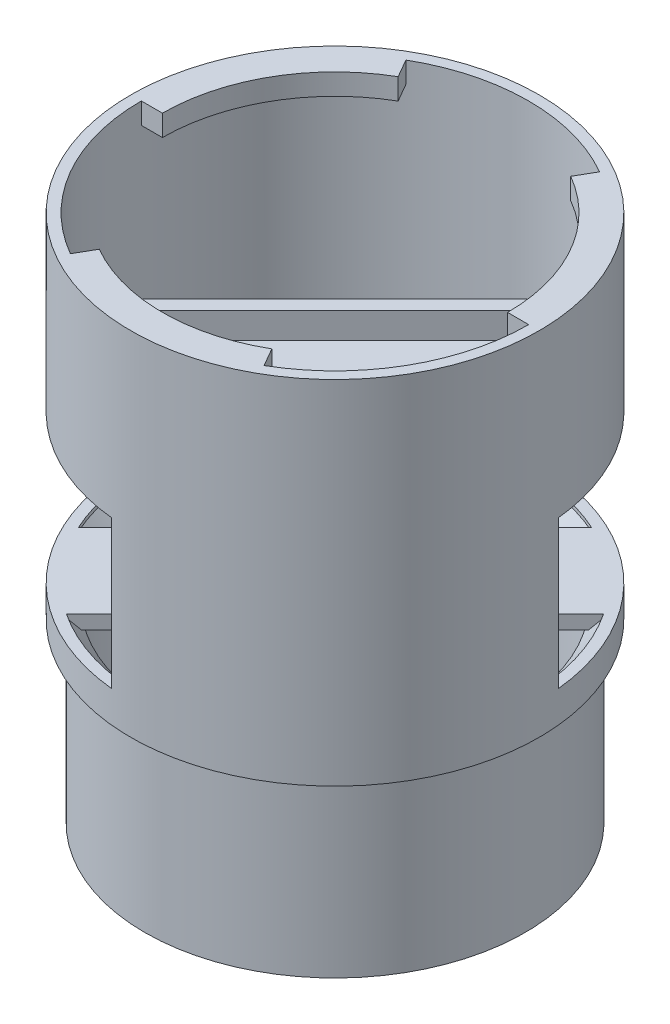
SolidWorks part; units mm, degrees
ref_plane "Front Plane" through (0, 0, 0) normal (0, 0, 1) x (1, 0, 0)
ref_plane "Top Plane" through (0, 0, 0) normal (0, 1, 0) x (1, 0, 0)
ref_plane "Right Plane" through (0, 0, 0) normal (1, 0, 0) x (0, 0, -1)
sketch "Sketch1" plane through (0, 0, 0) normal (0, 1, 0) x (1, 0, 0)
  circle A0 centre (0, 0) radius 25.5
  circle A1 centre (0, 0) radius 27
  dimension "D1" = 54
  dimension "D2" = 1.5
extrude "Boss-Extrude3" add sketch "Sketch1" along normal blind 25
sketch "Sketch3" plane through (0, 0, 0) normal (0, -1, 0) x (1, 0, 0)
  line L0 (-25.5, 0) -> (25.5, 0) construction
  line L1 (0, 25.5) -> (0, -25.5) construction
  line L2 (-25.1843, 4) -> (-14.4568, 4)
  line L3 (-4, 14.4568) -> (-4, 25.1843)
  line L4 (14.4568, 4) -> (25.1843, 4)
  line L5 (4, 25.1843) -> (4, 14.4568)
  line L6 (4, -14.4568) -> (4, -25.1843)
  line L7 (25.1843, -4) -> (14.4568, -4)
  line L8 (-14.4568, -4) -> (-25.1843, -4)
  line L9 (-4, -25.1843) -> (-4, -14.4568)
  circle A0 centre (0, 0) radius 25.5 construction
  arc A1 (-25.1843, 4) -> (-25.1843, -4) centre (0, 0) ccw
  arc A2 (4, 25.1843) -> (-4, 25.1843) centre (0, 0) ccw
  arc A3 (25.1843, -4) -> (25.1843, 4) centre (0, 0) ccw
  arc A4 (-4, -25.1843) -> (4, -25.1843) centre (0, 0) ccw
  circle A5 centre (-10, 0) radius 1.75
  circle A6 centre (0, 10) radius 1.75
  circle A7 centre (10, 0) radius 1.75
  circle A8 centre (0, -10) radius 1.75
  circle A9 centre (0, 0) radius 5
  arc A10 (-14.4568, -4) -> (-4, -14.4568) centre (0, 0) ccw
  arc A11 (-4, 14.4568) -> (-14.4568, 4) centre (0, 0) ccw
  arc A12 (14.4568, 4) -> (4, 14.4568) centre (0, 0) ccw
  arc A13 (4, -14.4568) -> (14.4568, -4) centre (0, 0) ccw
  point P22 (0, 0)
  point P32 (0, 0)
  dimension "D4" = 3.5
  dimension "D7" = 10
  dimension "D8" = 30
  dimension "D1" = 4
  dimension "D2" = 4
  dimension "D5" = 10
  dimension "D3" = 4
  dimension "D6" = 4
extrude "Boss-Extrude4" add sketch "Sketch3" against normal blind 6
ref_plane "Plane1" through (0, 0, 0) normal (-0.7071, 0, 0.7071) x (0.7071, 0, 0.7071)
sketch "Sketch4" plane through (0, 0, 0) normal (-0.7071, 0, 0.7071) x (0.7071, 0, 0.7071)
  line L0 (0, 0) -> (0, 105.4419) construction
  line L1 (-27, 25) -> (-29, 25)
  line L2 (27, 25) -> (-27, 25) construction
  line L3 (-20.2823, 75) -> (15.9379, 75) construction
  line L4 (25.5, 25) -> (-25.5, 25) construction
  line L5 (-29, 25) -> (-29, 75)
  line L6 (-29, 75) -> (-27.5, 75)
  line L7 (-27.5, 75) -> (-27.5, 29)
  line L8 (-27.5, 29) -> (-25.5, 27)
  line L9 (-29, 41.2871) -> (-29, 82.0597) construction
  line L10 (-25.5, 27) -> (-25.5, 25)
  line L11 (-25.5, 25) -> (-27, 25)
  line L15 (0, 75) -> (0, 73.5)
  line L16 (0, 75) -> (0, 73.5)
  dimension "D1" = 50
  dimension "D2" = 29
  dimension "D3" = 1.5
  dimension "D4" = 50
  dimension "D5" = 2
  dimension "D6" = 135
revolve "Revolve1" add sketch "Sketch4" angle 360 about L0 region at (-19.8899, 48.2634, -19.8899)
sketch "Sketch5" plane through (0, 0, 0) normal (-0.7071, 0, 0.7071) x (0.7071, 0, 0.7071)
  line L0 (0, 82.5379) -> (0.5211, 25.5117) construction
  line L2 (-17.6113, 29.5) -> (18.3887, 29.5)
  line L3 (-17.6113, 29.5) -> (-17.6113, 50.5)
  line L4 (-17.6113, 50.5) -> (18.3887, 50.5)
  line L5 (18.3887, 29.5) -> (18.3887, 50.5)
  line L6 (-17.6113, 29.5) -> (18.3887, 50.5) construction
  line L7 (-17.6113, 50.5) -> (18.3887, 29.5) construction
  line L8 (27.5, 29) -> (-27.5, 29) construction
  point P2 (0.3887, 40)
  dimension "D1" = 11
  dimension "D2" = 21
  dimension "D3" = 36
extrude "Cut-Extrude1" cut sketch "Sketch5" against normal through all both and the other way through all
sketch "Sketch6" plane through (0, 0, 0) normal (-0.7071, 0, 0.7071) x (0.7071, 0, 0.7071)
  line L2 (-17.6113, 50.5) -> (18.3887, 50.5) construction
  line L6 (-19.6113, 29.5) -> (-17.6113, 29.5)
  line L8 (-9.6113, 29.5) -> (5.3887, 29.5)
  line L9 (5.3887, 29.5) -> (5.3887, 27.5)
  line L10 (5.3887, 27.5) -> (-9.6113, 27.5)
  line L11 (-9.6113, 27.5) -> (-9.6113, 29.5)
  line L14 (-17.6113, 29.5) -> (-17.6113, 50.5)
  line L15 (-17.6113, 50.5) -> (-19.6113, 50.5)
  line L16 (-19.6113, 50.5) -> (-19.6113, 29.5)
  line L17 (-9.6113, 50.5) -> (-9.6113, 52.5)
  line L19 (-9.6113, 52.5) -> (5.83, 52.5)
  line L20 (5.83, 52.5) -> (5.83, 50.5)
  line L21 (5.83, 50.5) -> (-9.6113, 50.5)
  dimension "D1" = 2
  dimension "D2" = 2
  dimension "D3" = 21
  dimension "D4" = 2
  dimension "D5" = 15
  dimension "D6" = 8
extrude "Boss-Extrude6" add sketch "Sketch6" against normal up to next and the other way up to next
sketch "Sketch7" plane through (0, 75, 0) normal (0, 1, 0) x (1, 0, 0)
  line L0 (-29, 0) -> (29, 0) construction
  line L1 (-27.5, 0) -> (-24.5, 0)
  line L2 (-12.25, 21.2176) -> (-13.75, 23.8157)
  circle A0 centre (0, 0) radius 29 construction
  arc A1 (-13.75, 23.8157) -> (-27.5, 0) centre (0, 0) ccw
  arc A2 (-12.25, 21.2176) -> (-24.5, 0) centre (0, 0) ccw
  circle A3 centre (0, 0) radius 24.5 construction
  circle A4 centre (0, 0) radius 27.5 construction
  dimension "D2" = 60
  dimension "D1" = 3
extrude "Boss-Extrude7" add sketch "Sketch7" against normal blind 3
ref_axis "Axis1" through (0, 75, 0) along (0, -1, 0)
pattern_circular "CirPattern1" count 3 over 360 about axis through (0, 75, 0) along (0, -1, 0) of "Boss-Extrude7"
fillet "Fillet1" radius 10 4 edges at (0, 6, 25.5) (-25.5, 6, 0) (0, 6, -25.5) (25.5, 6, 0)
